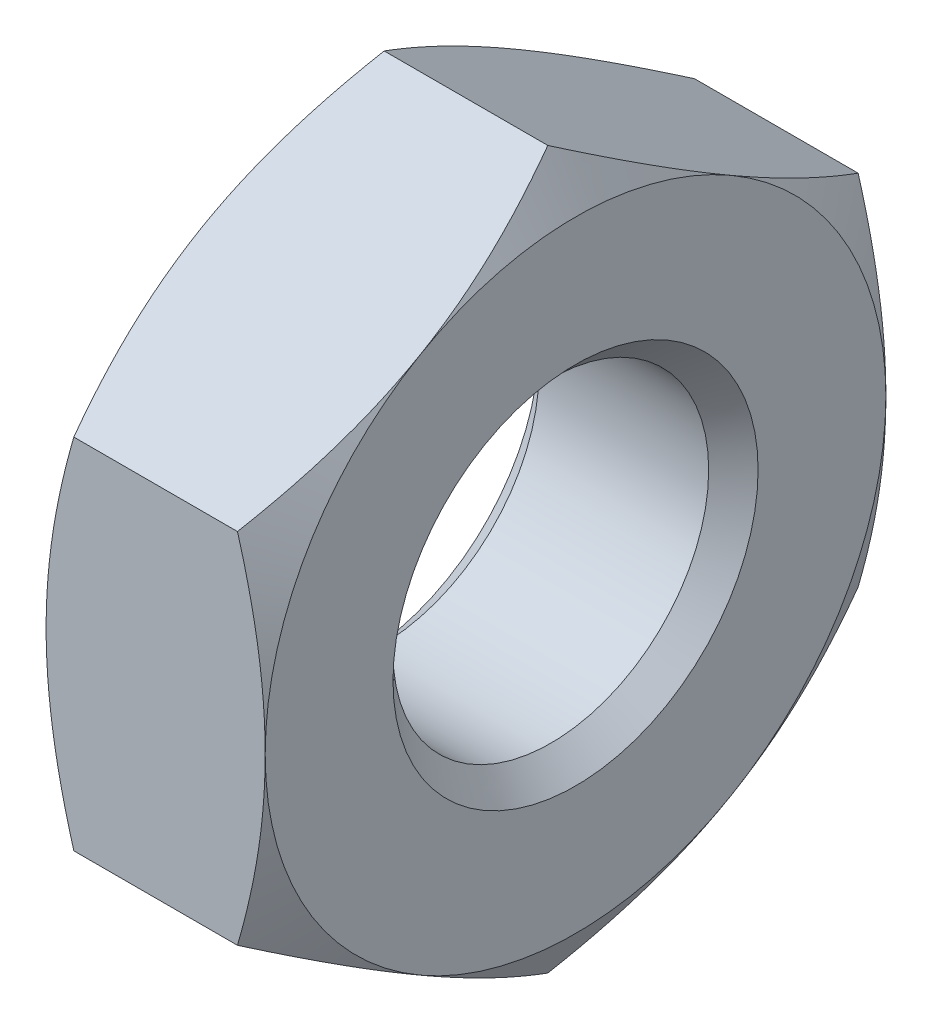
SolidWorks part; units mm, degrees
ref_plane "前视基准面" through (0, 0, 0) normal (0, 0, 1) x (1, 0, 0)
ref_plane "上视基准面" through (0, 0, 0) normal (0, 1, 0) x (1, 0, 0)
ref_plane "右视基准面" through (0, 0, 0) normal (1, 0, 0) x (0, 0, -1)
sketch "草图1" plane through (0, 0, 0) normal (0, 0, 1) x (1, 0, 0)
  line L0 (-3, 0) -> (-3, 8.5)
  line L1 (-3, 8.5) -> (-2.0185, 10.2)
  line L2 (-2.0185, 10.2) -> (2.0185, 10.2)
  line L3 (2.0185, 10.2) -> (3, 8.5)
  line L4 (3, 8.5) -> (3, 0)
  line L5 (3, 0) -> (-3, 0)
  line L6 (3, 0) -> (-3, 0) construction
revolve "旋转1" add sketch "草图1" angle 360 about L6 reverse direction yes
sketch "草图2" plane through (0, 0, 0) normal (0, 0, 1) x (1, 0, 0)
  line L0 (-3, 0) -> (-3, 5)
  line L1 (-3, 5) -> (-2.3235, 4.3235)
  line L2 (-2.3235, 4.3235) -> (2.3235, 4.3235)
  line L3 (2.3235, 4.3235) -> (3, 5)
  line L4 (3, 5) -> (3, 0)
  line L5 (3, 0) -> (-3, 0)
  line L6 (3, 0) -> (-3, 0) construction
revolve "切除-旋转1" cut sketch "草图2" angle 360 about L6 reverse direction yes
cosmetic thread "装饰螺纹线1" parameters "D1"=6, "D2"=10
sketch "草图3" plane through (0, 0, 0) normal (1, 0, 0) x (0, 0, -1)
  line L0 (-17, 17) -> (-17, -17)
  line L1 (-17, -17) -> (17, -17)
  line L2 (17, -17) -> (17, 17)
  line L3 (17, 17) -> (-17, 17)
  line L4 (-8.5, -4.9075) -> (0, -9.815)
  line L5 (0, -9.815) -> (8.5, -4.9075)
  line L6 (8.5, -4.9075) -> (8.5, 4.9075)
  line L7 (8.5, 4.9075) -> (0, 9.815)
  line L8 (0, 9.815) -> (-8.5, 4.9075)
  line L9 (-8.5, 4.9075) -> (-8.5, -4.9075)
extrude "切除-拉伸1" cut sketch "草图3" along normal blind 3 and the other way blind 3
ref_plane "nut1 XY" through (0, 0, 0) normal (-1, 0, 0) x (0, 0, 1)
ref_plane "nut1 XZ" through (0, 0, 0) normal (0, 1, 0) x (1, 0, 0)
ref_plane "nut1 YZ" through (0, 0, 0) normal (0, 0, -1) x (-1, 0, 0)
ref_axis "nut1 X" through (0, 0, 80.9) along (0, 0, -1)
ref_axis "nut1 Y" through (0, 50, 0) along (0, -1, 0)
ref_axis "nut1 Z" through (-80.9, 0, 0) along (1, 0, 0)
sketch3d "nut1"
  point P0 (0, 0, 0)
